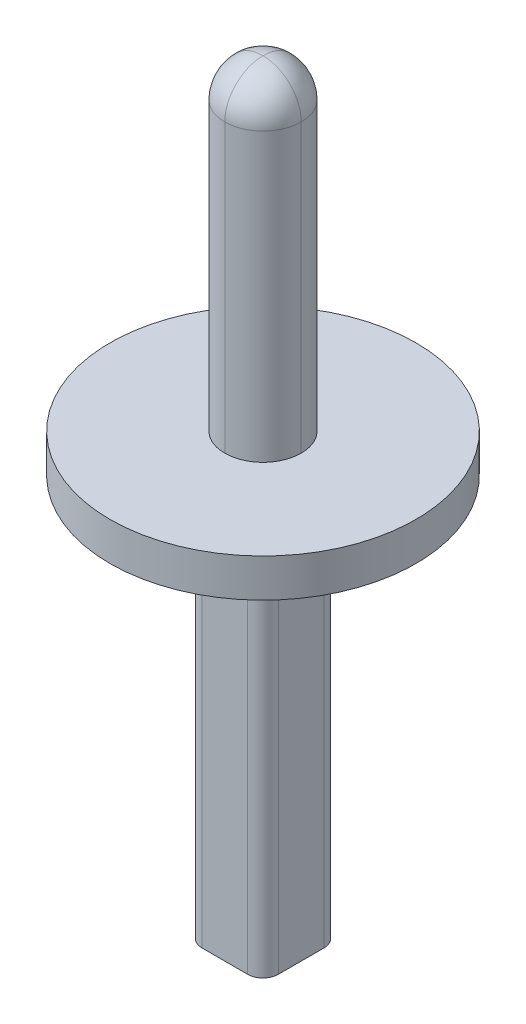
SolidWorks part; units mm, degrees
ref_plane "Front Plane" through (0, 0, 0) normal (0, 0, 1) x (1, 0, 0)
ref_plane "Top Plane" through (0, 0, 0) normal (0, 1, 0) x (1, 0, 0)
ref_plane "Right Plane" through (0, 0, 0) normal (1, 0, 0) x (0, 0, -1)
sketch "Sketch1" plane through (0, 0, 0) normal (0, 1, 0) x (1, 0, 0)
  line L1 (-5, -5) -> (5, -5)
  line L2 (-5, -5) -> (-5, 5)
  line L3 (-5, 5) -> (5, 5)
  line L4 (5, -5) -> (5, 5)
  line L5 (-5, -5) -> (5, 5) construction
  line L6 (-5, 5) -> (5, -5) construction
  point P0 (0, 0)
  dimension "D1" = 10
  dimension "D2" = 10
extrude "Boss-Extrude1" add sketch "Sketch1" along normal mid plane 100
sketch "Sketch2" plane through (0, 50, 0) normal (0, 1, 0) x (1, 0, 0)
  line L1 (-5, 5) -> (5, 5)
  line L2 (-5, 5) -> (-5, -5)
  line L3 (-5, -5) -> (5, -5)
  line L4 (5, 5) -> (5, -5)
  circle A0 centre (0, 0) radius 20
  dimension "D1" = 40
extrude "Boss-Extrude2" add sketch "Sketch2" along normal mid plane 5 from offset 45 offset against normal yes
fillet "Fillet2" radius 2 4 edges at (-5, -23.75, -5) (5, -23.75, -5) (-5, -23.75, 5) (5, -23.75, 5)
fillet "Fillet3" radius 5 4 edges at (-5, 28.75, -5) (-5, 28.75, 5) (5, 28.75, 5) (5, 28.75, -5)
fillet "Fillet4" radius 5 4 edges at (3.5355, 50, 3.5355) (-3.5355, 50, 3.5355) (-3.5355, 50, -3.5355) (3.5355, 50, -3.5355)
scale "Scale1" bodies to scale 102 scale about centroid uniform scaling yes scale factor 1.5
